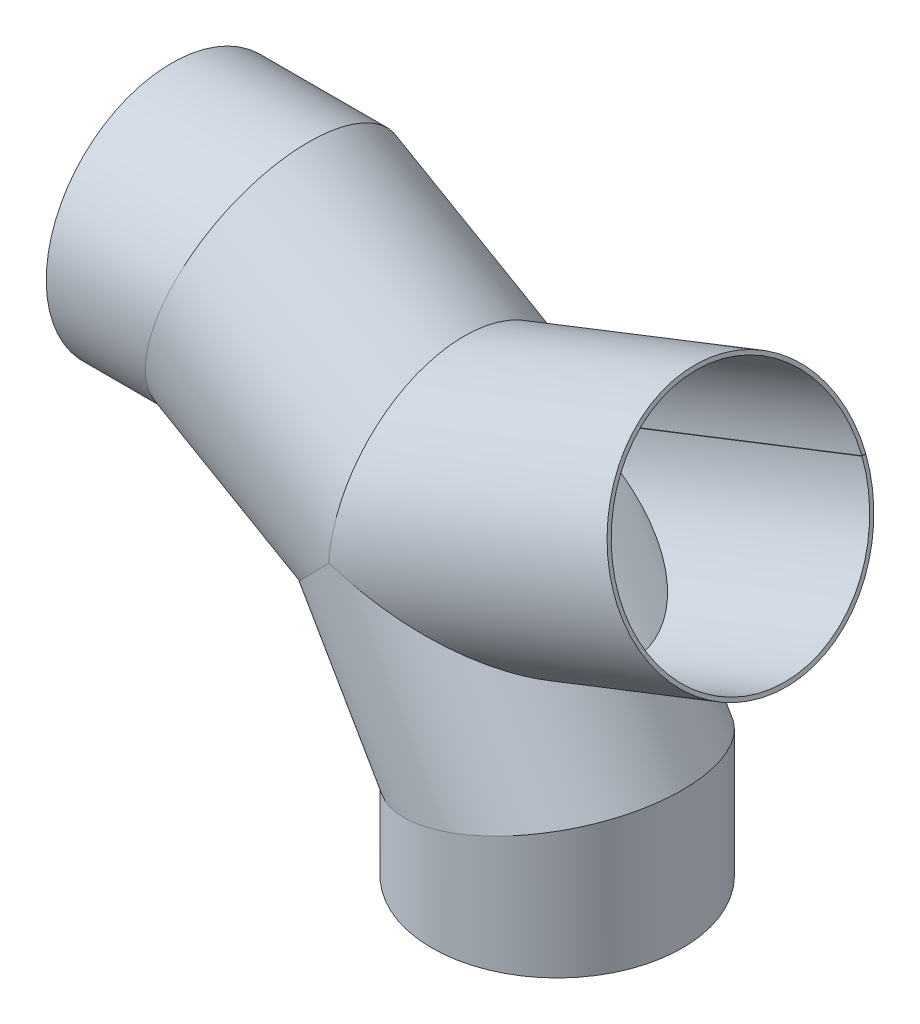
SolidWorks part; units mm, degrees
ref_plane "前视基准面" through (0, 0, 0) normal (0, 0, 1) x (1, 0, 0)
ref_plane "上视基准面" through (0, 0, 0) normal (0, 1, 0) x (1, 0, 0)
ref_plane "右视基准面" through (0, 0, 0) normal (1, 0, 0) x (0, 0, -1)
sketch "草图1" plane through (0, 0, 0) normal (0, 0, 1) x (1, 0, 0)
  line L0 (0, 0) -> (0, 267.9492) construction
  line L1 (0, 267.9492) -> (-267.9492, 732.0508) construction
  line L2 (-267.9492, 732.0508) -> (-732.0508, 1000) construction
  line L3 (-732.0508, 1000) -> (-1000, 1000) construction
  line L4 (-325, 0) -> (325, 0) construction
  line L5 (0, 0) -> (-1000, 0) construction
  line L6 (-1000, 0) -> (-1000, 1000) construction
  line L7 (-732.0508, 1000) -> (-1000, 0) construction
  line L8 (-1000, 0) -> (0, 267.9492) construction
  line L9 (-267.9492, 732.0508) -> (-1000, 0) construction
  line L10 (-500, 866.0254) -> (-1000, 0) construction
  line L11 (-1000, 0) -> (-133.9746, 500) construction
  line L12 (-267.9492, 732.0508) -> (475.2146, 1022.8225) construction
  line L13 (356.796, 1325.4807) -> (593.6333, 720.1642) construction
  line L14 (0, 267.9492) -> (325, 355.0327) construction
  line L15 (-1000, 1000) -> (-1000, 1325) construction
  line L16 (-732.0508, 1000) -> (-644.9673, 1325) construction
  line L17 (-133.9746, 500) -> (147.4837, 662.5) construction
  line L18 (-500, 866.0254) -> (-337.5, 1147.4837) construction
  line L19 (325, 0) -> (325, 355.0327) construction
  line L20 (325, 355.0327) -> (-30.0327, 969.9673) construction
  line L21 (-30.0327, 969.9673) -> (-644.9673, 1325) construction
  line L22 (-644.9673, 1325) -> (-1000, 1325) construction
  line L23 (-325, 0) -> (-325, 180.8657) construction
  line L24 (-325, 180.8657) -> (-505.8657, 494.1343) construction
  line L25 (-505.8657, 494.1343) -> (-819.1343, 675) construction
  line L26 (-819.1343, 675) -> (-1000, 675) construction
  line L27 (356.796, 1325.4807) -> (-240.8107, 1091.66) construction
  line L28 (593.6333, 720.1642) -> (202.5378, 567.1435) construction
  line L29 (-1000, 0) -> (-1000, -10) construction
  line L30 (-240.8107, 1091.66) -> (-267.9492, 732.0508) construction
  line L31 (-267.9492, 732.0508) -> (202.5378, 567.1435) construction
  line L33 (-267.9492, 732.0508) -> (475.2146, 1022.8225)
  dimension "D1" = 30
  dimension "d" = 650
  dimension "R" = 1000
  dimension "hm" = 798.023
  dimension "t" = 10
  dimension "bb" = 81.369
sketch "草图2" plane through (0, 0, 0) normal (0, 1, 0) x (1, 0, 0)
  line L0 (-1000, 325) -> (-1000, -325) construction
  line L1 (0, 325) -> (0, -325) construction
  circle A0 centre (0, 0) radius 325
extrude "拉伸-薄壁1" add sketch "草图2" along normal up to vertex (355.0327 mm away) thin up to point (325, 355.0327, 0) thin type one direction reverse wall 10
ref_plane "基准面1" through (-250, 433.0127, 0) normal (0.5, -0.866, 0) x (0.866, 0.5, 0)
ref_plane "基准面2" through (-750, 433.0127, 0) normal (-0.866, 0.5, 0) x (0, 0, 1)
ref_plane "基准面3" through (-1000, 0, 0) normal (1, 0, 0) x (0, 0, -1)
sketch "草图3" plane through (-250, 433.0127, 0) normal (0.5, -0.866, 0) x (0.866, 0.5, 0)
  circle A0 centre (133.9746, 0) radius 325
extrude "拉伸-薄壁2" add sketch "草图3" against normal up to vertex (355.0327 mm away) and the other way up to vertex (355.0327 mm away) separate body thin up to point (-30.0327, 969.9673, 0) other way up to point (325, 355.0327, 0) thin type one direction reverse wall 10
sketch "草图4" plane through (-750, 433.0127, 0) normal (-0.866, 0.5, 0) x (0, 0, 1)
  circle A0 centre (0, 500) radius 325
extrude "拉伸-薄壁3" add sketch "草图4" along normal up to vertex (355.0327 mm away) and the other way up to vertex (355.0327 mm away) separate body thin up to point (-644.9673, 1325, 0) other way up to point (-30.0327, 969.9673, 0) thin type one direction reverse wall 10
sketch "草图5" plane through (-1000, 0, 0) normal (1, 0, 0) x (0, 0, -1)
  circle A0 centre (0, 1000) radius 325
extrude "拉伸-薄壁4" add sketch "草图5" along normal up to vertex (355.0327 mm away) separate body thin up to point (-644.9673, 1325, 0) thin type one direction reverse wall 10
ref_plane "基准面4" through (475.2146, 1022.8225, 0) normal (0.9313, 0.3644, 0) x (-0.3644, 0.9313, 0)
sketch "草图6" plane through (475.2146, 1022.8225, 0) normal (0.9313, 0.3644, 0) x (-0.3644, 0.9313, 0)
  line L0 (0, -325) -> (0, 325) construction
  circle A0 centre (0, 0) radius 325
extrude "拉伸-薄壁5" add sketch "草图6" against normal up to vertex (798.023 mm away) separate body thin up to point (-267.9492, 732.0508, 0) thin type one direction reverse wall 10
sketch "草图11" plane through (0, 0, 0) normal (0, 0, 1) x (1, 0, 0)
  line L0 (-1000, 0) -> (325, 355.0327)
sketch "草图12" plane through (0, 0, 0) normal (0, 0, 1) x (1, 0, 0)
  line L0 (-1000, 0) -> (-644.9673, 1325)
extrude "切除-拉伸3" cut sketch "草图11" against normal through all and the other way through all
extrude "切除-拉伸4" cut sketch "草图11<2>" against normal through all and the other way through all flip side to cut
sketch "草图11<2>" plane through (0, 0, 0) normal (0, 0, 1) x (1, 0, 0) same geometry as "草图11"
extrude "切除-拉伸5" cut sketch "草图12" against normal through all and the other way through all flip side to cut
extrude "切除-拉伸6" cut sketch "草图12<2>" against normal through all and the other way through all
sketch "草图12<2>" plane through (0, 0, 0) normal (0, 0, 1) x (1, 0, 0) same geometry as "草图12"
sketch "草图13" plane through (0, 0, 0) normal (0, 0, 1) x (1, 0, 0)
  line L0 (-240.8107, 1091.66) -> (-267.9492, 732.0508)
  line L1 (-267.9492, 732.0508) -> (202.5378, 567.1435)
  line L2 (-267.9492, 732.0508) -> (202.5378, 567.1435) construction
  line L3 (-240.8107, 1091.66) -> (-267.9492, 732.0508) construction
  line L4 (-30.0327, 969.9673) -> (-644.9673, 1325) construction
  line L5 (356.796, 1325.4807) -> (-240.8107, 1091.66) construction
  line L6 (202.5378, 567.1435) -> (593.6333, 720.1642)
  line L7 (593.6333, 720.1642) -> (356.796, 1325.4807)
  line L8 (356.796, 1325.4807) -> (-240.8107, 1091.66)
  line L9 (325, 355.0327) -> (-30.0327, 969.9673) construction
extrude "切除-拉伸1" cut sketch "草图13" against normal through all and the other way through all flip side to cut
extrude "切除-拉伸2" cut sketch "草图13<2>" against normal through all and the other way through all
sketch "草图13<2>" plane through (0, 0, 0) normal (0, 0, 1) x (1, 0, 0) same geometry as "草图13"
sketch "草图14" plane through (0, 0, 0) normal (0, 0, 1) x (1, 0, 0)
  line L1 (-1000, -10) -> (939.9346, 1949.9346)
extrude "切除-拉伸7" cut sketch "草图14" against normal through all and the other way through all
extrude "切除-拉伸8" cut sketch "草图14<2>" against normal through all and the other way through all flip side to cut
sketch "草图14<2>" plane through (0, 0, 0) normal (0, 0, 1) x (1, 0, 0) same geometry as "草图14"
sketch "草图7" plane through (0, 0, 0) normal (0, 1, 0) x (1, 0, 0)
  line L0 (0, 0) -> (-325, 0)
  circle A0 centre (0, 0) radius 325 construction
extrude "切除-拉伸-薄壁2" cut sketch "草图7" along normal through all thin thin type mid plane wall 1
sketch "草图8" plane through (-250, 433.0127, 0) normal (0.5, -0.866, 0) x (0.866, 0.5, 0)
  line L0 (133.9746, 0) -> (-191.0254, 0)
  circle A0 centre (133.9746, 0) radius 325 construction
extrude "切除-拉伸-薄壁3" cut sketch "草图8" against normal through all and the other way through all thin thin type mid plane wall 1
sketch "草图9" plane through (-750, 433.0127, 0) normal (-0.866, 0.5, 0) x (0, 0, 1)
  line L0 (0, 500) -> (0, 175)
  circle A0 centre (0, 500) radius 325 construction
extrude "切除-拉伸-薄壁4" cut sketch "草图9" against normal through all and the other way through all thin thin type mid plane wall 1
sketch "草图10" plane through (-1000, 0, 0) normal (1, 0, 0) x (0, 0, -1)
  line L0 (0, 1000) -> (0, 675)
  circle A0 centre (0, 1000) radius 325 construction
extrude "切除-拉伸-薄壁6" cut sketch "草图10" along normal through all thin thin type mid plane wall 1
extrude "切除-拉伸-薄壁7" cut sketch "草图1" against normal through all thin thin type mid plane wall 1
equation "\"D5@拉伸-薄壁1\" = \"t@草图1\""
equation "\"D5@拉伸-薄壁2\" = \"t@草图1\""
equation "\"D5@拉伸-薄壁3\" = \"t@草图1\""
equation "\"D5@拉伸-薄壁4\" = \"t@草图1\""
equation "\"D5@拉伸-薄壁5\" = \"t@草图1\""
